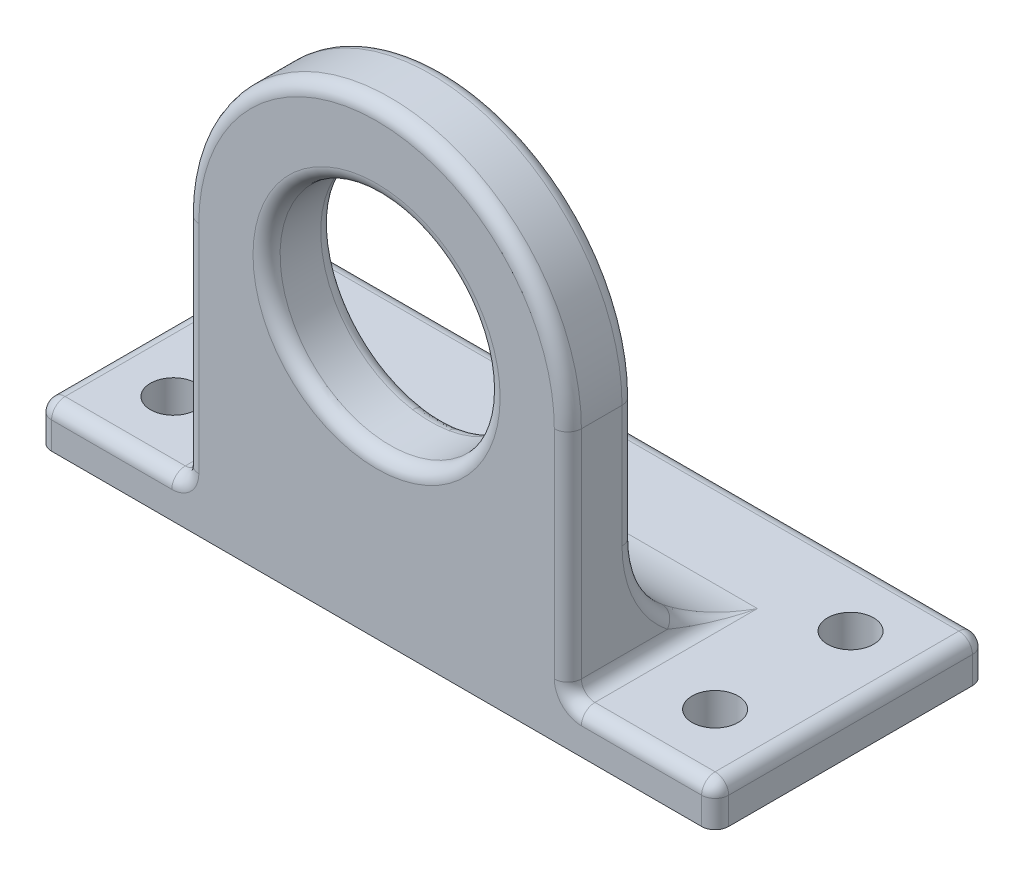
SolidWorks part; units mm, degrees
ref_plane "Alzado" through (0, 0, 0) normal (0, 0, 1) x (1, 0, 0)
ref_plane "Planta" through (0, 0, 0) normal (0, 1, 0) x (1, 0, 0)
ref_plane "Vista lateral" through (0, 0, 0) normal (1, 0, 0) x (0, 0, -1)
sketch "Croquis1" plane through (0, 0, 0) normal (0, 0, 1) x (1, 0, 0)
  line L0 (0, 0) -> (0, -20) construction
  line L1 (-14.125, 0) -> (-14.125, -20)
  line L2 (14.125, 0) -> (14.125, -20)
  line L3 (-14.125, -20) -> (14.125, -20)
  line L5 (-25, -17) -> (25, -17)
  line L6 (-25, -17) -> (-25, -20)
  line L7 (-25, -20) -> (25, -20)
  line L8 (25, -17) -> (25, -20)
  circle A0 centre (0, 0) radius 8.125
  circle A1 centre (0, 0) radius 14.125
  dimension "D2" = 16.25
  dimension "D1" = 20
  dimension "D4" = 50
  dimension "D5" = 3
  dimension "D3" = 6
extrude "Saliente-Extruir1" add sketch "Croquis1" along normal blind 5 contours A0 A1 | L0 A1 L1 L5 | A1 L0 L5 L2 | L5 L0 L7 L2 | L0 L5 L1 L3 | L6 L7 L1 L5 | L8 L5 L2 L7 region at (-9.7054, -9.7054, 0) region at (9.0679, -13.2055, 0) region at (-9.0679, -13.2055, 0) region at (7.0625, -18.5, 0) region at (-7.0625, -18.5, 0) region at (-19.5625, -18.5, 0) region at (19.5625, -18.5, 0)
extrude "Saliente-Extruir2" add sketch "Croquis1<3>" against normal blind 15 contours L6 L7 L1 L5 | L0 L5 L1 L3 | L5 L0 L7 L2 | L8 L5 L2 L7 region at (7.0625, -18.5, 0) region at (-7.0625, -18.5, 0) region at (-19.5625, -18.5, 0) region at (19.5625, -18.5, 0)
sketch "Croquis1<3>" plane through (0, 0, 0) normal (0, 0, 1) x (1, 0, 0) same geometry as "Croquis1"
hole_wizard "Taladro de margen para M31" positions "Croquis2" profile "Croquis3" hole size "M3" standard "ISO" end condition through all
sketch "Croquis2" plane through (0, -17, 0) normal (0, 1, 0) x (1, 0, 0)
  line L0 (0, -1000) -> (0, 49000) construction
  point P0 (-20, 0)
  point P2 (-20, 10)
  point P11 (20, 0)
  point P12 (20, 10)
  dimension "D2" = 10
  dimension "D3" = 40
sketch "Croquis3" plane through (-20, -17, 0) normal (1, 0, 0) x (0, 0, 1)
  line L0 (0, 0) -> (0, 3)
  line L1 (0, 3) -> (1.7, 3)
  line L2 (1.7, 3) -> (1.7, 0)
  line L5 (1.7, 0) -> (0, 0)
  line L11 (0, -6.35) -> (0, 107.95) construction
  dimension "Diámetro de taladro hasta el siguiente" = 3.4
  dimension "Profundidad de taladro hasta el siguiente" = 3
fillet "Redondeo1" radius 8 1 edges at (0, -17, 0)
fillet "Redondeo2" radius 1 2 edges at (-14.125, -17, -1.5) (14.125, -17, -1.5)
fillet "Redondeo3" radius 1 16 edges at (14.3396, -16.6189, -5.5603) (14.125, -13.063, -1.1086) (14.125, -4.5, 0) (-14.3396, -16.6189, -5.5603) (-14.125, -13.063, -1.1086) (-14.125, -4.5, 0) (20.0625, -17, 5) (14.4179, -16.7071, 5) (14.125, -8, 5) (-20.0625, -17, 5) (-14.4179, -16.7071, 5) (-14.125, -8, 5) (0, 14.125, 0) (8.125, 0, 0) (0, 14.125, 5) (8.125, 0, 5)
fillet "Redondeo4" radius 1 9 edges at (-25, -19, 5) (-25, -17.2929, 4.7071) (25, -19, 5) (25, -17.2929, 4.7071) (-25, -18.5, -15) (25, -18.5, -15) (-25, -17, -5.5) (0, -17, -15) (25, -17, -5.5)
